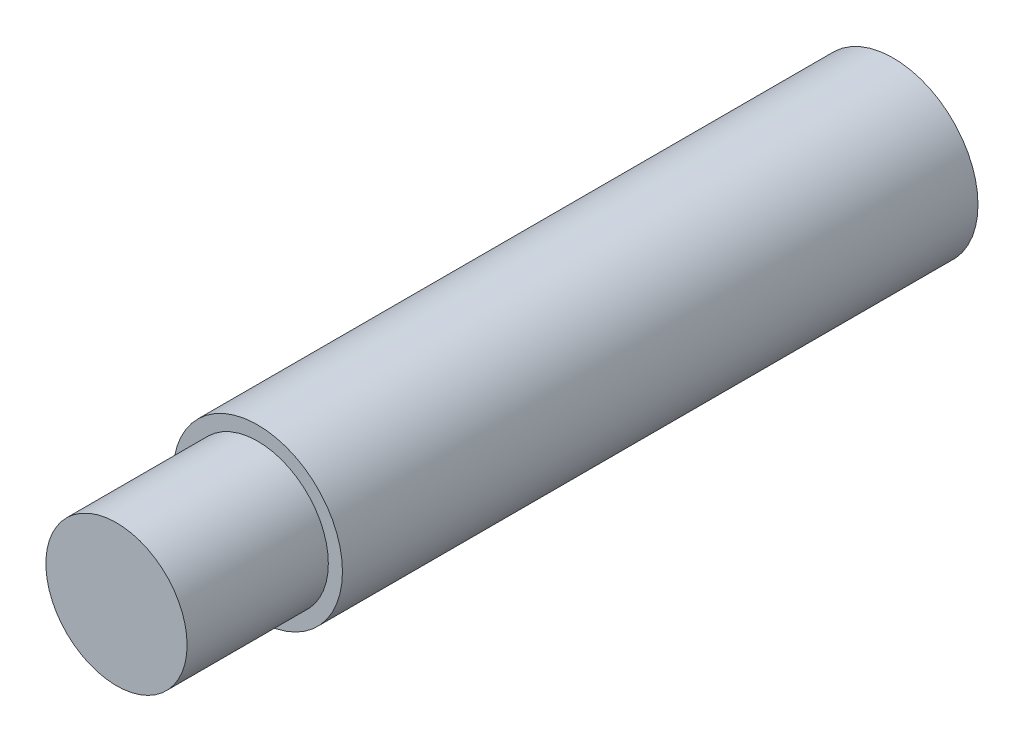
SolidWorks part; units mm, degrees
material "1060 Alloy"
ref_plane "Front Plane" through (0, 0, 0) normal (0, 0, 1) x (1, 0, 0)
ref_plane "Top Plane" through (0, 0, 0) normal (0, 1, 0) x (1, 0, 0)
ref_plane "Right Plane" through (0, 0, 0) normal (1, 0, 0) x (0, 0, -1)
sketch "Sketch6" plane through (0, 0, 0) normal (1, 0, 0) x (0, 0, -1)
  line L0 (0, 0) -> (43, 0)
  line L1 (43, 0) -> (43, 3.5)
  line L2 (43, 3.5) -> (55, 3.5)
  line L3 (55, 3.5) -> (55, 6)
  line L4 (55, 6) -> (10, 6)
  line L5 (10, 6) -> (10, 5)
  line L6 (10, 5) -> (0, 5)
  line L7 (0, 5) -> (0, 0)
  dimension "D1" = 10
  dimension "D2" = 5
  dimension "D3" = 6
  dimension "D4" = 45
  dimension "D5" = 3.5
  dimension "D6" = 12
revolve "Revolve1" add sketch "Sketch6" angle 360 about L0
